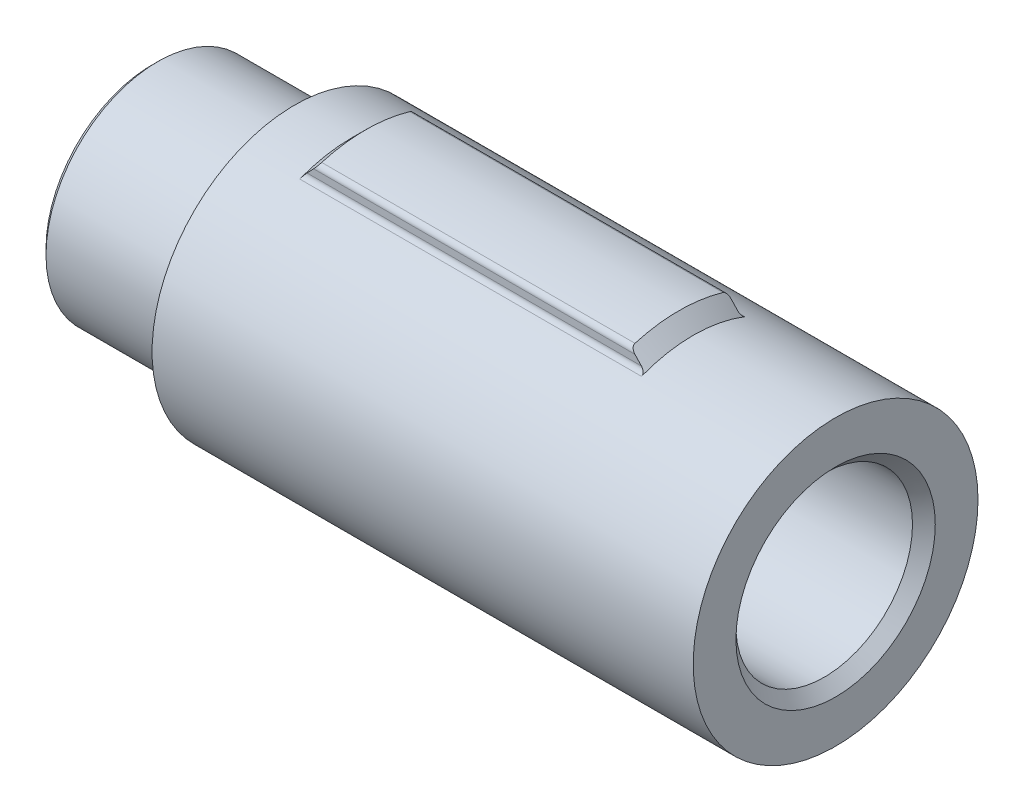
SolidWorks part; units mm, degrees
ref_plane "前视基准面" through (0, 0, 0) normal (0, 0, 1) x (1, 0, 0)
ref_plane "上视基准面" through (0, 0, 0) normal (0, 1, 0) x (1, 0, 0)
ref_plane "右视基准面" through (0, 0, 0) normal (1, 0, 0) x (0, 0, -1)
other "Configuration Table"
sketch "草图1" plane through (0, 0, 0) normal (1, 0, 0) x (0, 0, -1)
  circle A0 centre (0, 0) radius 5
  dimension "D1" = 10
extrude "凸台-拉伸1" add sketch "草图1" along normal blind 19
sketch "草图3" plane through (19, 0, 0) normal (1, 0, 0) x (0, 0, -1)
  circle A0 centre (0, 0) radius 3.1
  dimension "D1" = 6.2
extrude "切除-拉伸1" cut sketch "草图3" against normal blind 17
sketch "草图5" plane through (2, 0, 0) normal (1, 0, 0) x (0, 0, -1)
  line L1 (-1.6882, 2.6) -> (1.6882, 2.6)
  line L2 (-1.6882, 2.6) -> (-1.6882, 5.2345)
  line L3 (1.6882, 2.6) -> (1.6882, 5.2345)
  line L4 (0, 5.5) -> (1.6882, 5.5) construction
  line L5 (-1.6882, 5.5) -> (0, 5.5) construction
  line L6 (-1.6882, 5.2345) -> (-1.6882, 5.5) construction
  line L7 (1.6882, 5.2345) -> (1.6882, 5.5) construction
  circle A0 centre (0, 0) radius 3.1 construction
  arc A1 (1.6882, 2.6) -> (-1.6882, 2.6) centre (0, 0) ccw construction
  arc A2 (-1.6882, 2.6) -> (1.6882, 2.6) centre (0, 0) ccw construction
  arc A5 (-1.6882, 5.2345) -> (1.6882, 5.2345) centre (0, 0) ccw construction
  circle A6 centre (0, 0) radius 5.5
  arc A7 (1.6882, 5.2345) -> (-1.6882, 5.2345) centre (0, 0) ccw
  dimension "D1" = 2.6
  dimension "D2" = 0.5
extrude "凸台-拉伸2" add sketch "草图5" along normal blind 12
sketch "草图8" plane through (0, 0, 0) normal (-1, 0, 0) x (0, 0, 1)
  circle A0 centre (0, 0) radius 3.925
  dimension "D1" = 7.85
extrude "凸台-拉伸4" add sketch "草图8" along normal blind 5
sketch "草图9" plane through (-5, 0, 0) normal (-1, 0, 0) x (0, 0, 1)
  circle A0 centre (0, 0) radius 2.75
  dimension "D1" = 5.5
extrude "切除-拉伸2" cut sketch "草图9" against normal blind 5
sketch "草图10" plane through (0, 0, 0) normal (-1, 0, 0) x (0, 0, 1)
  line L1 (0.7217, 1.25) -> (-0.7217, 1.25)
  line L2 (-0.7217, 1.25) -> (-1.4434, 0)
  line L3 (-1.4434, 0) -> (-0.7217, -1.25)
  line L4 (-0.7217, -1.25) -> (0.7217, -1.25)
  line L5 (0.7217, -1.25) -> (1.4434, 0)
  line L6 (1.4434, 0) -> (0.7217, 1.25)
  circle A0 centre (0, 0) radius 1.25 construction
  dimension "D1" = 2.5
extrude "凸台-拉伸5" add sketch "草图10" along normal blind 3.2
fillet "圆角1" radius 0.2 4 edges at (8, 4.7064, -1.6882) (8, 5.2345, -1.6882) (8, 4.7064, 1.6882) (8, 5.2345, 1.6882)
chamfer "倒角1" distance 0.5 angle 45 3 edges at (14, 5.5, 0) (2, 5.5, 0) (14, 2.6, 0)
chamfer "倒角2" distance 0.4 angle 45 1 edges at (19, 0, -3.1)
chamfer "倒角3" distance 0.2 angle 45 8 edges at (-3.2, -0.625, 1.0825) (-3.2, -1.25, 0) (-3.2, -0.625, -1.0825) (-3.2, 0.625, -1.0825) (-3.2, 1.25, 0) (-3.2, 0.625, 1.0825) (-5, 0, 3.925) (-5, 0, 2.75)
